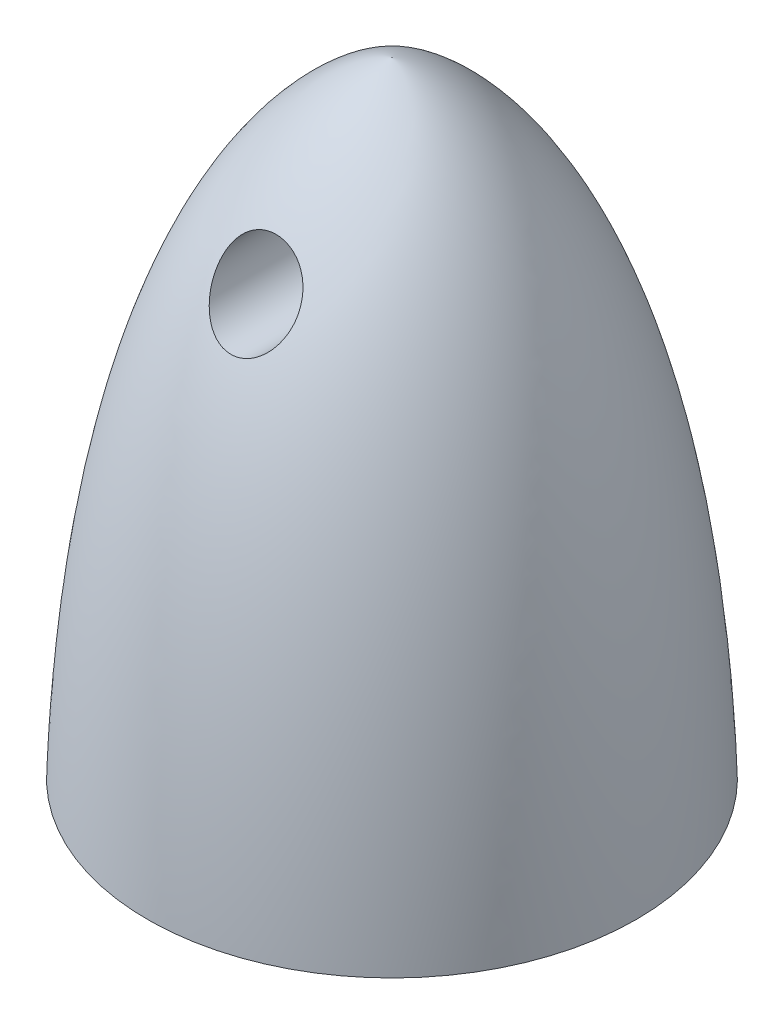
SolidWorks part; units mm, degrees
ref_plane "Front Plane" through (0, 0, 0) normal (0, 0, 1) x (1, 0, 0)
ref_plane "Top Plane" through (0, 0, 0) normal (0, 1, 0) x (1, 0, 0)
ref_plane "Right Plane" through (0, 0, 0) normal (1, 0, 0) x (0, 0, -1)
sketch "Sketch1" plane through (0, 0, 0) normal (0, 0, 1) x (1, 0, 0)
  line L0 (3.5, 3.5284) -> (3.5, 0)
  line L1 (3.5, 0) -> (9, 0)
  line L4 (0, 23) -> (0, 14)
  line L6 (3.5, 3.5284) -> (3.5, 14)
  line L7 (3.5, 14) -> (0, 14)
  line L8 (0, 0) -> (0, 11.9245) construction
  spline S0 degree 3 poles (0, 23) (0.0373, 22.984) (8.2621, 21.4802) (9, 0) knots 0 0 0 0 1 1 1 1
  dimension "D2" = 23
  dimension "D1" = 3.5
  dimension "5.5mm" = 5.5
  dimension "D3" = 14
revolve "Revolve1" add sketch "Sketch1" angle 360 about L8
sketch "Sketch2" plane through (0, 0, 0) normal (0, 1, 0) x (1, 0, 0)
  line L1 (5.6292, 0) -> (2.8146, 4.875)
  line L2 (2.8146, 4.875) -> (-2.8146, 4.875)
  line L3 (-2.8146, 4.875) -> (-5.6292, 0)
  line L4 (-5.6292, 0) -> (-2.8146, -4.875)
  line L5 (-2.8146, -4.875) -> (2.8146, -4.875)
  line L6 (2.8146, -4.875) -> (5.6292, 0)
  circle A0 centre (0, 0) radius 4.875 construction
  point P1 (0, 0)
  dimension "D1" = 9.75
extrude "Cut-Extrude1" cut sketch "Sketch2" along normal blind 7
sketch "Sketch4" plane through (0, 0, 0) normal (0, 0, 1) x (1, 0, 0)
  circle A0 centre (0, 18) radius 1.5
  point P4 (0, 0)
  dimension "D1" = 3
  dimension "D2" = 5
extrude "Cut-Extrude2" cut sketch "Sketch4" against normal mid plane 17
chamfer "Chamfer1" distance 0.5 angle 45 6 edges at (-4.2219, 0, 2.4375) (-4.2219, 0, -2.4375) (0, 0, -4.875) (0, 0, 4.875) (4.2219, 0, 2.4375) (4.2219, 0, -2.4375)
fillet "Fillet1" radius 0.5 2 edges at (3.5, 14, 0) (0, 7, 3.5)
